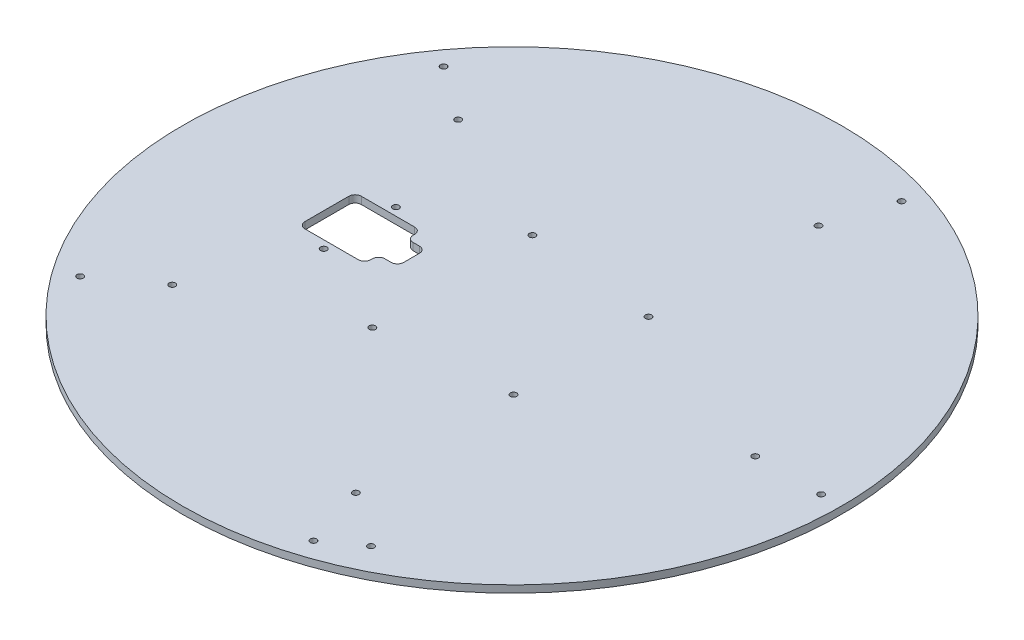
SolidWorks part; units mm, degrees
ref_plane "Front Plane" through (0, 0, 0) normal (0, 0, 1) x (1, 0, 0)
ref_plane "Top Plane" through (0, 0, 0) normal (0, 1, 0) x (1, 0, 0)
ref_plane "Right Plane" through (0, 0, 0) normal (1, 0, 0) x (0, 0, -1)
sketch "Sketch1" plane through (0, 0, 0) normal (0, 1, 0) x (1, 0, 0)
  circle A1 centre (0, 0) radius 266.7
  dimension "D1" = 533.4
extrude "Boss-Extrude1" add sketch "Sketch1" along normal blind 5.842
ref_axis "Axis1" through (0, 6.1341, 0) along (0, -1, 0)
sketch "Sketch2" plane through (0, 5.842, 0) normal (0, 1, 0) x (1, 0, 0)
  line L0 (55.88, 0) -> (0, 0) construction
  line L1 (0, 0) -> (-48.26, 0) construction
  line L2 (-48.26, 0) -> (-48.26, 64.77) construction
  line L3 (-48.26, 0) -> (-123.19, 0) construction
  line L4 (55.88, 54.61) -> (55.88, 0) construction
  line L5 (55.88, 0) -> (55.88, -54.61) construction
  line L6 (-123.19, 0) -> (-123.19, 29.21) construction
  line L7 (-48.26, -64.77) -> (-48.26, 0) construction
  line L10 (-123.19, -29.21) -> (-123.19, 0) construction
  circle A0 centre (55.88, 54.61) radius 2.5527
  circle A1 centre (-48.26, 64.77) radius 2.5527
  circle A2 centre (-48.26, -64.77) radius 2.5527
  circle A3 centre (55.88, -54.61) radius 2.5527
  circle A4 centre (-123.19, 29.21) radius 2.5527
  circle A5 centre (-123.19, -29.21) radius 2.5527
  dimension "D5" = 5.1054
  dimension "D1" = 129.54
  dimension "D2" = 109.22
  dimension "D3" = 55.88
  dimension "D4" = 48.26
  dimension "D6" = 58.42
  dimension "D7" = 123.19
extrude "Holes-MountingPolarMech" cut sketch "Sketch2" against normal through all
sketch "Sketch3" plane through (0, 5.842, 0) normal (0, 1, 0) x (1, 0, 0)
  line L0 (0, 0) -> (-96.52, 0) construction
  line L1 (-96.52, 0) -> (-123.19, 0) construction
  line L2 (-123.19, 0) -> (-123.19, 22.86) construction
  line L3 (-123.19, 0) -> (-123.19, -22.86) construction
  line L4 (-123.19, -22.86) -> (-123.19, -29.21) construction
  line L5 (-123.19, 22.86) -> (-123.19, 29.21) construction
  line L6 (-123.19, 0) -> (-149.86, 0) construction
  line L7 (-123.19, 22.86) -> (-149.86, 22.86)
  line L8 (-149.86, 22.86) -> (-149.86, 0)
  line L9 (-149.86, 0) -> (-149.86, -22.86)
  line L10 (-149.86, -22.86) -> (-123.19, -22.86)
  line L11 (-123.19, -22.86) -> (-96.52, -22.86)
  line L12 (-96.52, -22.86) -> (-96.52, -11.43)
  line L13 (-96.52, 11.43) -> (-96.52, 22.86)
  line L14 (-96.52, 22.86) -> (-123.19, 22.86)
  line L15 (-81.28, 0) -> (-81.28, -11.43)
  line L16 (-81.28, -11.43) -> (-96.52, -11.43)
  line L17 (-81.28, 0) -> (-81.28, 11.43)
  line L18 (-81.28, 11.43) -> (-96.52, 11.43)
  line L19 (-96.52, -11.43) -> (-96.52, 0) construction
  line L20 (-96.52, 0) -> (-96.52, 11.43) construction
  dimension "D1" = 45.72
  dimension "D2" = 22.86
  dimension "D3" = 15.24
  dimension "D4" = 53.34
extrude "Cutout-StepperMotorRelief" cut sketch "Sketch3" against normal through all
fillet "Fillet-StepperMotorRelief" radius 5.08 8 edges at (-149.86, 2.921, -22.86) (-149.86, 2.921, 22.86) (-96.52, 2.921, -22.86) (-96.52, 2.921, -11.43) (-81.28, 2.921, -11.43) (-96.52, 2.921, 11.43) (-81.28, 2.921, 11.43) (-96.52, 2.921, 22.86)
sketch "Sketch4" plane through (0, 5.842, 0) normal (0, 1, 0) x (1, 0, 0)
  line L0 (0, 0) -> (196.85, 0) construction
  line L1 (196.85, 0) -> (250.19, 0) construction
  circle A0 centre (250.19, 0) radius 2.5527
  circle A1 centre (196.85, 0) radius 2.5527
  dimension "D3" = 5.1054
  dimension "D1" = 196.85
  dimension "D2" = 53.34
extrude "Holes-Feet" cut sketch "Sketch4" against normal through all
pattern_circular "CirPattern-Feet" count 5 over 360 about axis through (0, 6.1341, 0) along (0, -1, 0) of "Holes-Feet"
sketch "Sketch5" plane through (0, 0, 0) normal (0, -1, 0) x (1, 0, 0)
  line L2 (77.313, 237.9448) -> (60.83, 187.2155) construction
  line L3 (74.1733, 228.2821) -> (104.3694, 218.4708) construction
  circle A2 centre (104.3694, 218.4708) radius 2.5527
  dimension "D1" = 31.75
  dimension "D4" = 5.1054
  dimension "D2" = 43.18
extrude "Cut-Extrude1" cut sketch "Sketch5" against normal through all
